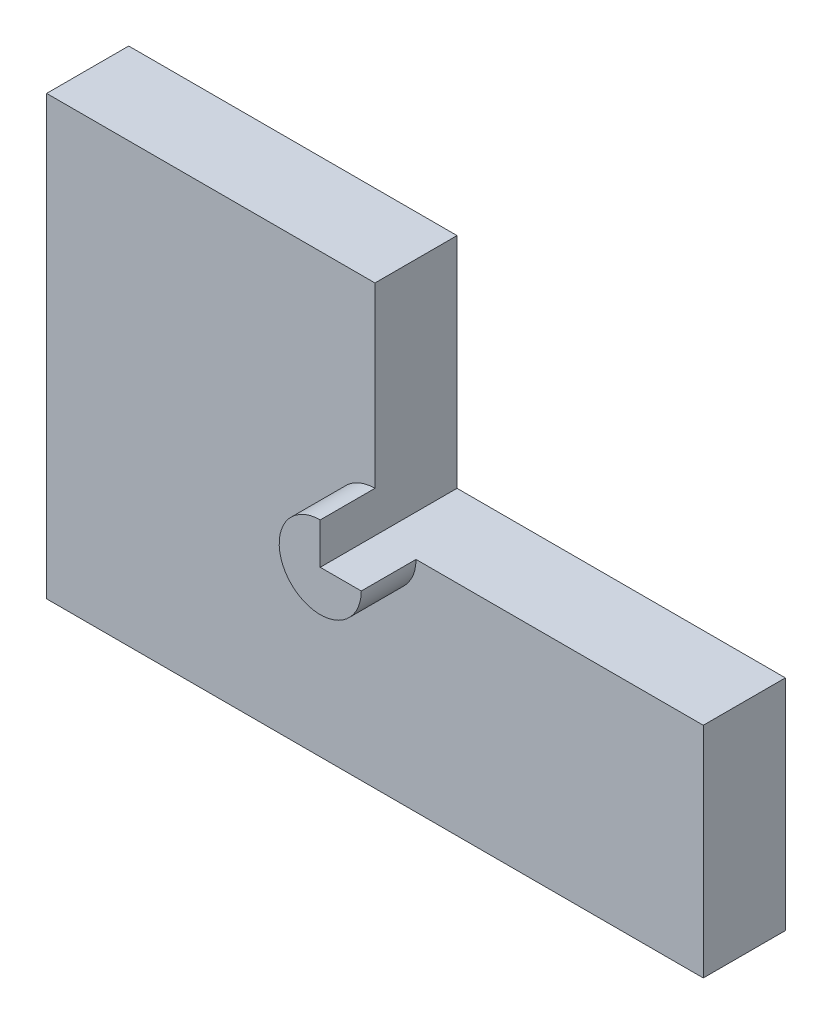
SolidWorks part; units mm, degrees
ref_plane "Front Plane" through (0, 0, 0) normal (0, 0, 1) x (1, 0, 0)
ref_plane "Top Plane" through (0, 0, 0) normal (0, 1, 0) x (1, 0, 0)
ref_plane "Right Plane" through (0, 0, 0) normal (1, 0, 0) x (0, 0, -1)
sketch "Sketch1" plane through (0, 0, 0) normal (0, 0, 1) x (1, 0, 0)
  line L1 (0, 101.6) -> (152.4, 101.6)
  line L2 (0, 101.6) -> (0, 0)
  line L3 (0, 0) -> (152.4, 0)
  line L4 (152.4, 101.6) -> (152.4, 0)
  point P4 (0, 0)
  point P5 (0, 0)
  dimension "D1" = 101.6
  dimension "D2" = 152.4
extrude "Boss-Extrude1" add sketch "Sketch1" along normal blind 19.05
sketch "Sketch4" plane through (0, 0, 19.05) normal (0, 0, 1) x (1, 0, 0)
  line L1 (152.4, 101.6) -> (76.2, 101.6)
  line L2 (152.4, 101.6) -> (152.4, 50.8)
  line L3 (152.4, 50.8) -> (76.2, 50.8)
  line L4 (76.2, 101.6) -> (76.2, 50.8)
  circle A0 centre (76.2, 50.8) radius 9.525
  line M5 (152.4, 0) -> (152.4, 101.6)
  line M6 (152.4, 101.6) -> (0, 101.6)
  dimension "D3" = 19.05
  dimension "D1" = 50.8
  dimension "D2" = 76.2
extrude "Cut-Extrude1" cut sketch "Sketch4" against normal through all both contours L3 A0 L4 | A0 L3 L4 M5 M6 region at (114.9387, 76.6005, 19.05) region at (80.2425, 54.8425, 19.05)
extrude "Boss-Extrude2" add sketch "Sketch4<4>" along normal blind 12.7 contours L4 A0 L3 region at (74.8525, 49.4525, 19.05)
sketch "Sketch4<4>" plane through (0, 0, 19.05) normal (0, 0, 1) x (1, 0, 0) same geometry as "Sketch4"
